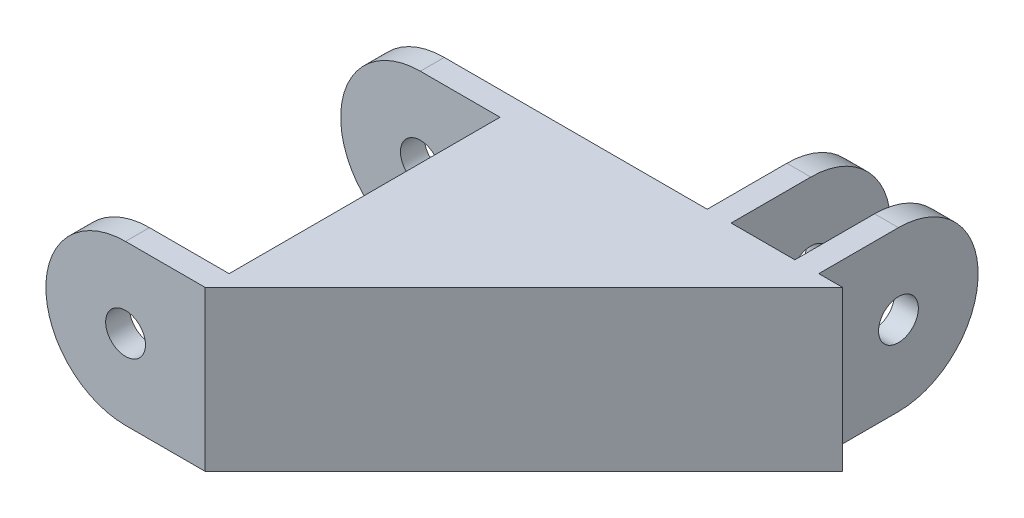
SolidWorks part; units mm, degrees
ref_plane "Front Plane" through (0, 0, 0) normal (0, 0, 1) x (1, 0, 0)
ref_plane "Top Plane" through (0, 0, 0) normal (0, 1, 0) x (1, 0, 0)
ref_plane "Right Plane" through (0, 0, 0) normal (1, 0, 0) x (0, 0, -1)
sketch "Sketch1" plane through (0, 0, 0) normal (0, 1, 0) x (1, 0, 0)
  line L0 (0, 0) -> (0, 40)
  line L1 (0, 40) -> (40, 40)
  line L2 (40, 40) -> (0, 0)
  dimension "D1" = 40
  dimension "D2" = 40
extrude "Boss-Extrude1" add sketch "Sketch1" along normal mid plane 20
sketch "Sketch2" plane through (0, 0, 0) normal (1, 0, 0) x (0, 0, -1)
  line L1 (40, 10) -> (50, 10)
  line L2 (40, 10) -> (40, -10)
  line L3 (40, -10) -> (50, -10)
  line L4 (0, -10) -> (40, -10)
  line L5 (0, 10) -> (0, -10)
  line L6 (40, 10) -> (0, 10)
  line L7 (40, -10) -> (40, 10)
  line L8 (0, -10) -> (40, -10) construction
  line L9 (0, 10) -> (0, -10) construction
  line L10 (40, 10) -> (0, 10) construction
  line L11 (40, -10) -> (40, 10) construction
  arc A0 (50, -10) -> (50, 10) centre (50, 0) ccw
  dimension "D2" = 10
  dimension "D3" = 10
  dimension "D1" = 0
extrude "Boss-Extrude2" add sketch "Sketch2" against normal blind 3 from offset 37
pattern_linear "LPattern1" count 2 spacing 11 along (-1, 0, 0) of "Boss-Extrude2"
sketch "Sketch3" plane through (0, 0, 0) normal (1, 0, 0) x (0, 0, -1)
  circle A0 centre (50, 0) radius 2.5
  dimension "D1" = 5
extrude "Cut-Extrude1" cut sketch "Sketch3" along normal blind 40
sketch "Sketch4" plane through (0, 0, 0) normal (0, 0, 1) x (1, 0, 0)
  line L0 (0, 10) -> (0, -10) construction
  line L1 (0, 10) -> (0, -10) construction
  line L3 (0, 10) -> (-10, 10)
  line L4 (0, 10) -> (0, -10)
  line L5 (0, -10) -> (-10, -10)
  arc A0 (-10, 10) -> (-10, -10) centre (-10, 0) ccw
  circle A1 centre (-10, 0) radius 2.5
  dimension "D2" = 10
  dimension "D3" = 5
  dimension "D1" = 10
extrude "Boss-Extrude3" add sketch "Sketch4" against normal blind 3
pattern_linear "LPattern2" count 2 spacing 37 along (0, 0, -1) of "Boss-Extrude3"
shell "Shell2" thickness 2 removed face at (32, 2.5, -40) removed face at (0, -2.5, -28.5)
